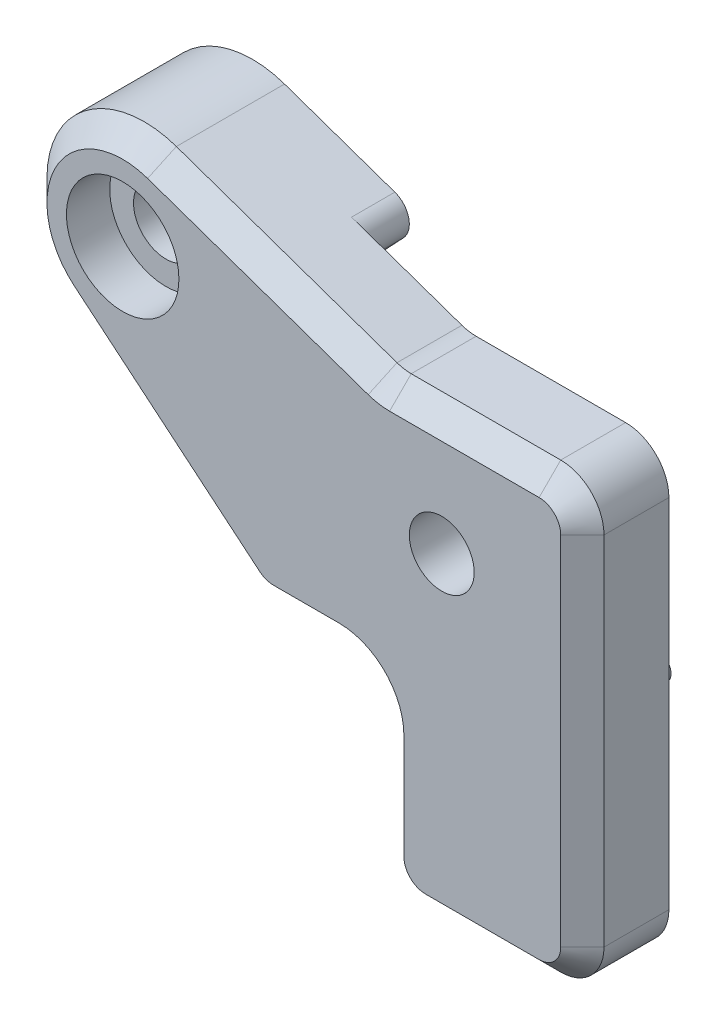
SolidWorks part; units mm, degrees
ref_plane "Front Plane" through (0, 0, 0) normal (0, 0, 1) x (1, 0, 0)
ref_plane "Top Plane" through (0, 0, 0) normal (0, 1, 0) x (1, 0, 0)
ref_plane "Right Plane" through (0, 0, 0) normal (1, 0, 0) x (0, 0, -1)
sketch "Sketch1" plane through (0, 0, 0) normal (0, 0, 1) x (1, 0, 0)
  line L0 (-2.75, -15) -> (-2.75, -6.15)
  line L1 (6.5, -15) -> (-2.75, -15)
  line L2 (6.5, -15) -> (6.5, 5.5)
  line L3 (6.5, 5.5) -> (-2.75, 5.5)
  line L7 (-13.2679, 9.1688) -> (-2.75, 5.5)
  line L8 (6.5, 5.5) -> (6.5, -15) construction
  line L9 (-2.75, 5.5) -> (6.5, 5.5) construction
  line L10 (-2.75, -6.15) -> (-2.75, -15) construction
  line L11 (6.5, -15) -> (-2.75, -15) construction
  line L12 (-2.75, -6.15) -> (-2.75, 5.5) construction
  line L13 (-17.6317, 1.4636) -> (-8.5, -6.15)
  line L14 (-8.5, -6.15) -> (-2.75, -6.15)
  line L15 (-2.75, -6.15) -> (-8.5, -6.15) construction
  line L16 (-16.25, 4.9199) -> (-19.25, 4.9199) construction
  circle A0 centre (0, 0) radius 1.25 construction
  circle A1 centre (0, 0) radius 1.5
  circle A2 centre (-14.75, 4.9199) radius 1.5
  arc A3 (-15.5, 3.6208) -> (-15.5, 6.2189) centre (-14.75, 4.9199) ccw construction
  arc A4 (-13.2679, 9.1688) -> (-17.6317, 1.4636) centre (-14.75, 4.9199) ccw
  dimension "D2" = 2.5
  dimension "D3" = 3
  dimension "D1" = 0.25
extrude "Boss-Extrude1" add sketch "Sketch1" against normal blind 2
fillet "Fillet1" radius 2 6 edges at (6.5, -15, -1) (-8.5, -6.15, -1) (-2.75, 5.5, -1) (6.5, 5.5, -1) (-2.75, -15, -1) (-2.75, -6.15, -1)
sketch "Sketch2" plane through (0, 0, 0) normal (0, 0, 1) x (1, 0, 0)
  line L7 (-0.75, -15) -> (4.5, -15)
  line L8 (6.5, -13) -> (6.5, 3.5)
  line L9 (4.5, 5.5) -> (-2.4112, 5.5)
  line L10 (-3.0699, 5.6116) -> (-13.2679, 9.1688)
  line L11 (-17.6317, 1.4636) -> (-9.0564, -5.6861)
  line L12 (-7.7756, -6.15) -> (-4.75, -6.15)
  line L13 (-2.75, -8.15) -> (-2.75, -13)
  line L14 (-0.75, -15) -> (4.5, -15)
  line L15 (6.5, -13) -> (6.5, 3.5)
  line L16 (4.5, 5.5) -> (-2.4112, 5.5)
  line L17 (-3.0699, 5.6116) -> (-13.2679, 9.1688)
  line L18 (-17.6317, 1.4636) -> (-9.0564, -5.6861)
  line L19 (-7.7756, -6.15) -> (-4.75, -6.15)
  line L20 (-2.75, -8.15) -> (-2.75, -13)
  circle A0 centre (0, 0) radius 1.5 construction
  circle A1 centre (0, 0) radius 1.5
  circle A2 centre (-14.75, 4.9199) radius 2.35 construction
  circle A3 centre (-14.75, 4.9199) radius 1.5 construction
  circle A4 centre (-14.75, 4.9199) radius 2.6
  arc A7 (4.5, -15) -> (6.5, -13) centre (4.5, -13) ccw
  arc A8 (6.5, 3.5) -> (4.5, 5.5) centre (4.5, 3.5) ccw
  arc A9 (-3.0699, 5.6116) -> (-2.4112, 5.5) centre (-2.4112, 7.5) ccw
  arc A10 (-13.2679, 9.1688) -> (-17.6317, 1.4636) centre (-14.75, 4.9199) ccw
  arc A11 (-9.0564, -5.6861) -> (-7.7756, -6.15) centre (-7.7756, -4.15) ccw
  arc A12 (-2.75, -8.15) -> (-4.75, -6.15) centre (-4.75, -8.15) ccw
  arc A13 (-2.75, -13) -> (-0.75, -15) centre (-0.75, -13) ccw
  arc A14 (4.5, -15) -> (6.5, -13) centre (4.5, -13) ccw
  arc A15 (6.5, 3.5) -> (4.5, 5.5) centre (4.5, 3.5) ccw
  arc A16 (-3.0699, 5.6116) -> (-2.4112, 5.5) centre (-2.4112, 7.5) ccw
  arc A17 (-13.2679, 9.1688) -> (-17.6317, 1.4636) centre (-14.75, 4.9199) ccw
  arc A18 (-9.0564, -5.6861) -> (-7.7756, -6.15) centre (-7.7756, -4.15) ccw
  arc A19 (-2.75, -8.15) -> (-4.75, -6.15) centre (-4.75, -8.15) ccw
  arc A20 (-2.75, -13) -> (-0.75, -15) centre (-0.75, -13) ccw
  dimension "D3" = 4.7
extrude "Boss-Extrude2" add sketch "Sketch2" along normal blind 2
chamfer "Chamfer1" distance 1 angle 45 14 edges at (1.875, -15, 2) (5.9142, -14.4142, 2) (-2.1642, -14.4142, 2) (6.5, -4.75, 2) (-2.75, -10.575, 2) (5.9142, 4.9142, 2) (-3.3358, -6.7358, 2) (1.0444, 5.5, 2) (-6.2628, -6.15, 2) (-2.7452, 5.5281, 2) (-8.4567, -6.0305, 2) (-8.1689, 7.3902, 2) (-13.344, -2.1113, 2) (-18.6656, 7.1375, 2)
sketch "Sketch3" plane through (0, 0, -2) normal (0, 0, -1) x (-1, 0, 0)
  line L0 (0, 0) -> (0, -9.5) construction
  circle A0 centre (0, -9.5) radius 1.25 construction
  circle A1 centre (0, -9.5) radius 1
  dimension "D3" = 2.5
  dimension "D1" = 9.5
extrude "Boss-Extrude3" add sketch "Sketch3" along normal blind 6
chamfer "Chamfer2" distance 3.5 distance2 0.4 1 edges at (-1, -9.5, -8) first distance on face at (-1, -9.5, -8)
sketch "Sketch4" plane through (0, 0, -2) normal (0, 0, -1) x (-1, 0, 0)
  line L0 (13.2679, 9.1688) -> (8.1689, 7.3902)
  line L1 (7.7709, 5.7597) -> (11.4769, 1.8317)
  line L2 (3.0699, 5.6116) -> (13.2679, 9.1688) construction
  circle A0 centre (14.75, 4.9199) radius 1.5 construction
  circle A1 centre (14.75, 4.9199) radius 1.5
  arc A4 (11.4769, 1.8317) -> (13.2679, 9.1688) centre (14.75, 4.9199) ccw
  arc A5 (17.6317, 1.4636) -> (13.2679, 9.1688) centre (14.75, 4.9199) ccw construction
  arc A6 (8.1689, 7.3902) -> (7.7709, 5.7597) centre (8.4983, 6.446) ccw
  point P14 (10.4164, 3.7073)
  point P15 (0, 0)
  point P16 (0, 0)
  point P17 (8.1689, 7.3902)
  dimension "D1" = 1
extrude "Boss-Extrude4" add sketch "Sketch4" along normal offset from surface (2 mm away) 6 up to face at (-3.0922, -3.4294, 2)
equation "\"Tolerance\" = 0.25mm"
equation "\"Pocket_Head_M5\"= 8mm"
equation "\"Pocket_Head_M4\" = 7mm"
equation "\"Pocket_Nut_M4\" = 7mm"
equation "\"Pocket_Nut_M5\"= 8mm"
equation "\"Pocket_Nut_M3\"= 5.5mm"
equation "\"Pocket_Head_M3\"= 5.5mm"
equation "\"D1@Sketch1\"=\"Tolerance\""
equation "\"D2@Sketch2\"=\"Tolerance\""
equation "\"Pocket_Head_M2.5\" = 4.7mm"
equation "\"D3@Sketch2\"=\"Pocket_Head_M2.5\""
equation "\"D2@Sketch3\"=\"Tolerance\""
